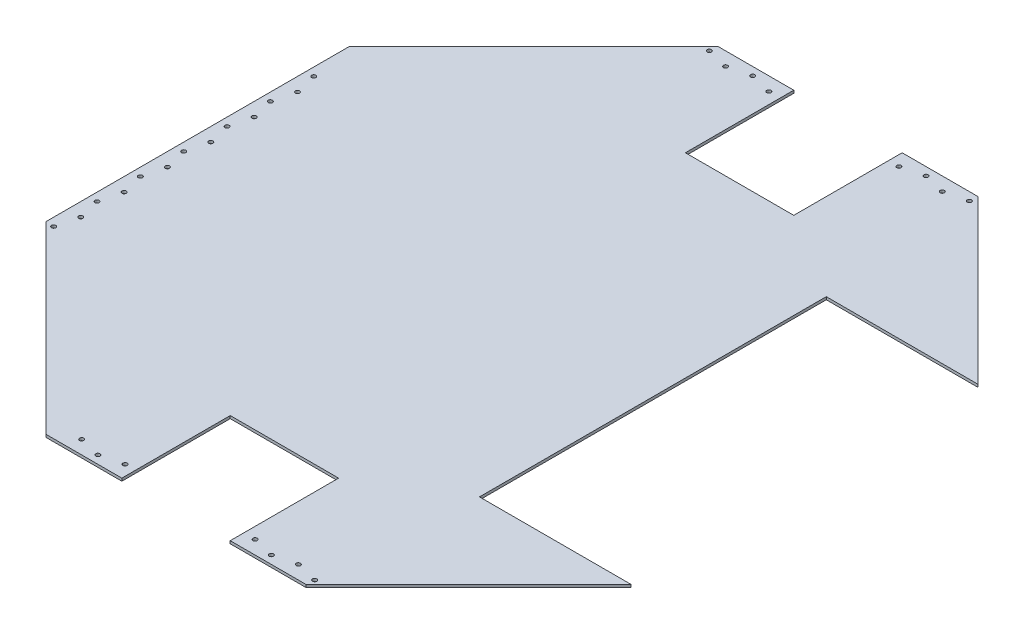
SolidWorks part; units mm, degrees
material "6061-T6 (SS)"
ref_plane "Front Plane" through (0, 0, 0) normal (0, 0, 1) x (1, 0, 0)
ref_plane "Top Plane" through (0, 0, 0) normal (0, 1, 0) x (1, 0, 0)
ref_plane "Right Plane" through (0, 0, 0) normal (1, 0, 0) x (0, 0, -1)
sketch "Sketch1" plane through (0, 0, 0) normal (0, 1, 0) x (1, 0, 0)
  line L0 (152.4, 393.7) -> (368.3, 177.8)
  line L1 (-152.4, -393.7) -> (152.4, -393.7)
  line L2 (-368.3, -177.8) -> (-368.3, 177.8)
  line L3 (-152.4, 393.7) -> (152.4, 393.7)
  line L4 (368.3, -177.8) -> (368.3, 177.8)
  line L5 (-368.3, -393.7) -> (368.3, 393.7) construction
  line L6 (-368.3, 393.7) -> (368.3, -393.7) construction
  line L7 (-368.3, 177.8) -> (-152.4, 393.7)
  line L8 (-368.3, -177.8) -> (-152.4, -393.7)
  line L9 (152.4, -393.7) -> (368.3, -177.8)
  point P0 (0, 0)
  dimension "D1" = 736.6
  dimension "D2" = 787.4
extrude "Boss-Extrude1" add sketch "Sketch1" along normal blind 3.175
sketch "Sketch2" plane through (0, 3.175, 0) normal (0, 1, 0) x (1, 0, 0)
  line L23 (368.3, -203.2) -> (165.1, -203.2)
  line L24 (368.3, -177.8) -> (368.3, 177.8) construction
  line L25 (165.1, -203.2) -> (165.1, 203.2)
  line L26 (165.1, 203.2) -> (368.3, 203.2)
  line L27 (368.3, 203.2) -> (368.3, -203.2)
  point P1 (368.3, 0)
  point P7 (368.3, 0)
  dimension "D1" = 406.4
  dimension "D2" = 203.2
extrude "Intake Cutout" cut sketch "Sketch2" against normal blind 3.175
sketch "Sketch3" plane through (0, 3.175, 0) normal (0, 1, 0) x (1, 0, 0)
  line L0 (-63.5, 393.7) -> (-63.5, 266.7)
  line L1 (152.4, 393.7) -> (-152.4, 393.7) construction
  line L2 (-63.5, 266.7) -> (63.5, 266.7)
  line L3 (63.5, 266.7) -> (63.5, 393.7)
  line L4 (63.5, 393.7) -> (-63.5, 393.7)
  line L5 (-152.4, -393.7) -> (152.4, -393.7) construction
  line L6 (-63.5, -393.7) -> (63.5, -393.7)
  line L7 (63.5, -393.7) -> (63.5, -266.7)
  line L8 (63.5, -266.7) -> (-63.5, -266.7)
  line L9 (-63.5, -266.7) -> (-63.5, -393.7)
  point P10 (0, -393.7)
  point P13 (0, -393.7)
  point P14 (0, 393.7)
  point P15 (0, 393.7)
  dimension "D1" = 127
  dimension "D2" = 127
extrude "Climber Cutout" cut sketch "Sketch3" against normal blind 3.175
hole_wizard "3/16 (0.195) Diameter Hole1" positions "Sketch5" profile "Sketch6" hole size "3/16" standard "ANSI Inch" end condition through all
sketch "Sketch5" plane through (0, 3.175, 0) normal (0, 1, 0) x (1, 0, 0)
  line L1 (-63.5, 393.7) -> (-152.4, 393.7) construction
  line L2 (-152.4, 393.7) -> (-368.3, 177.8) construction
  line L3 (-368.3, 177.8) -> (-368.3, -177.8) construction
  line L11 (63.5, -393.7) -> (152.4, -393.7) construction
  point P4 (-152.9447, 384.175)
  point P6 (-127.5447, 377.825)
  point P13 (-102.1447, 384.175)
  point P14 (-102.1447, 384.175)
  point P16 (-102.1447, 384.175)
  point P43 (-76.7447, 377.825)
  point P44 (-51.3447, 384.175)
  point P46 (-25.9447, 377.825)
  point P47 (-0.5447, 384.175)
  point P49 (24.8553, 377.825)
  point P50 (50.2553, 384.175)
  point P52 (75.6553, 377.825)
  point P53 (101.0553, 384.175)
  point P55 (126.4553, 377.825)
  point P56 (151.8553, 384.175)
  point P64 (-102.1447, 384.175)
  point P66 (-51.3447, 384.175)
  point P68 (-0.5447, 384.175)
  point P70 (50.2553, 384.175)
  point P72 (101.0553, 384.175)
  point P74 (151.8553, 384.175)
  point P76 (202.6553, 384.175)
  point P315 (409.575, 178.3447)
  point P316 (403.225, 152.9447)
  point P317 (409.575, 127.5447)
  point P318 (409.575, 127.5447)
  point P319 (409.575, 127.5447)
  point P320 (403.225, 102.1447)
  point P321 (409.575, 76.7447)
  point P322 (403.225, 51.3447)
  point P323 (409.575, 25.9447)
  point P324 (403.225, 0.5447)
  point P325 (409.575, -24.8553)
  point P326 (403.225, -50.2553)
  point P327 (409.575, -75.6553)
  point P328 (403.225, -101.0553)
  point P329 (409.575, -126.4553)
  point P330 (361.95, -170.9053)
  point P333 (152.9447, -384.175)
  point P334 (152.9447, -384.175)
  point P335 (152.9447, -384.175)
  point P336 (127.5447, -377.825)
  point P337 (102.1447, -384.175)
  point P338 (76.7447, -377.825)
  point P339 (51.3447, -384.175)
  point P340 (25.9447, -377.825)
  point P341 (0.5447, -384.175)
  point P342 (-24.8553, -377.825)
  point P343 (-50.2553, -384.175)
  point P344 (-75.6553, -377.825)
  point P345 (-101.0553, -384.175)
  point P347 (-358.775, -178.3447)
  point P348 (-352.425, -152.9447)
  point P349 (-358.775, -127.5447)
  point P350 (-358.775, -127.5447)
  point P351 (-358.775, -127.5447)
  point P352 (-352.425, -102.1447)
  point P353 (-358.775, -76.7447)
  point P354 (-352.425, -51.3447)
  point P355 (-358.775, -25.9447)
  point P356 (-352.425, -0.5447)
  point P357 (-358.775, 24.8553)
  point P358 (-352.425, 50.2553)
  point P359 (-358.775, 75.6553)
  point P360 (-352.425, 101.0553)
  point P361 (-358.775, 126.4553)
  point P382 (177.2553, 377.825)
  point P401 (-126.4553, -377.825)
  point P404 (-127.5447, -377.825)
  point P405 (0, 0)
  point P406 (178.3447, -377.825)
  point P407 (0, 0)
  point P408 (203.7447, -384.175)
  dimension "D1" = 25.4
  dimension "D2" = 25.4
  dimension "D3" = 9.525
  dimension "D4" = 15.875
  dimension "D5" = 6.35
  dimension "D7" = 50.8
  dimension "D9" = 9.525
  dimension "D10" = 9.525
  dimension "D11" = 25.4
  dimension "D12" = 6.35
  dimension "D6" = 7
  dimension "D8" = 4
sketch "Sketch6" plane through (-152.9447, 3.175, -384.175) normal (1, 0, 0) x (0, 0, 1)
  line L0 (0, 0) -> (0, 3.175)
  line L1 (0, 3.175) -> (2.4765, 3.175)
  line L2 (2.4765, 3.175) -> (2.4765, 0)
  line L5 (2.4765, 0) -> (0, 0)
  line L11 (0, -6.35) -> (0, 107.95) construction
  dimension "Thru Hole Dia." = 4.953
  dimension "Thru Hole Depth" = 3.175
